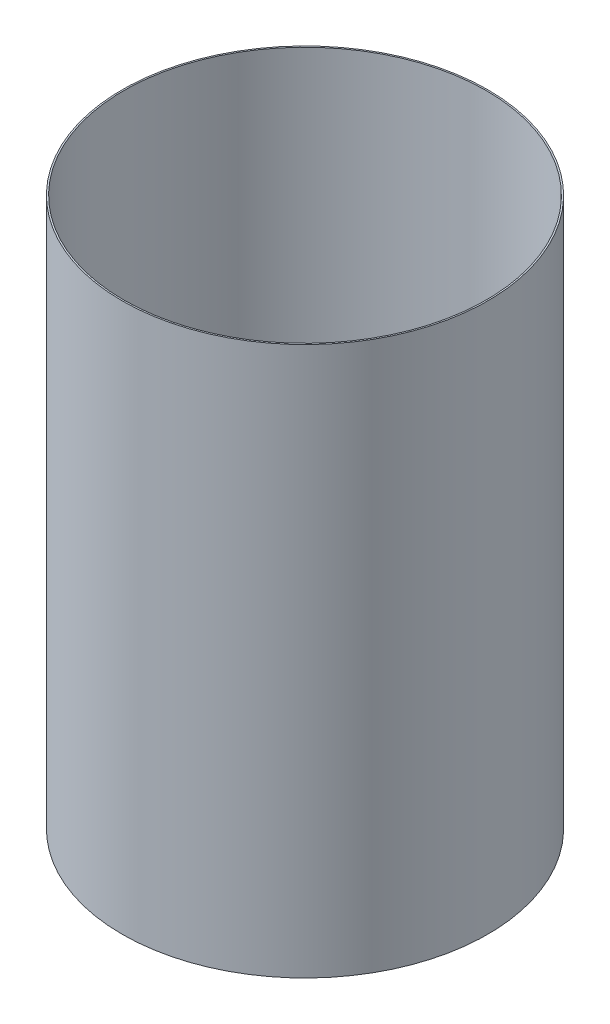
SolidWorks part; units mm, degrees
ref_plane "Front Plane" through (0, 0, 0) normal (0, 0, 1) x (1, 0, 0)
ref_plane "Top Plane" through (0, 0, 0) normal (0, 1, 0) x (1, 0, 0)
ref_plane "Right Plane" through (0, 0, 0) normal (1, 0, 0) x (0, 0, -1)
sketch "Sketch2" plane through (0, 0, 0) normal (0, 1, 0) x (1, 0, 0)
  circle A0 centre (0, 0) radius 151.13
  circle A1 centre (0, 0) radius 152.4
  dimension "D1" = 152.4
  dimension "D2" = 151.13
extrude "Boss-Extrude1" add sketch "Sketch2" along normal blind 457.2
